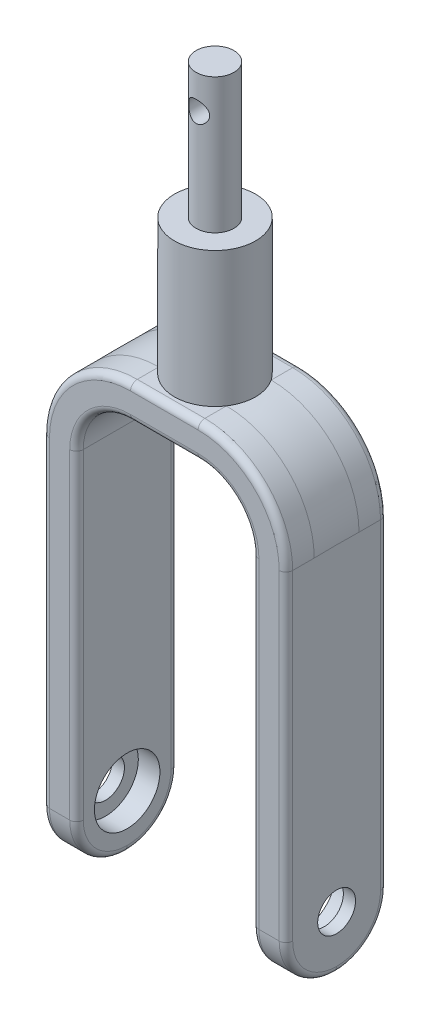
SolidWorks part; units mm, degrees
ref_plane "前视基准面" through (0, 0, 0) normal (0, 0, 1) x (1, 0, 0)
ref_plane "上视基准面" through (0, 0, 0) normal (0, 1, 0) x (1, 0, 0)
ref_plane "右视基准面" through (0, 0, 0) normal (1, 0, 0) x (0, 0, -1)
sketch "草图1" plane through (0, 0, 0) normal (0, 1, 0) x (1, 0, 0)
  line L1 (18, 7.5) -> (-18, 7.5)
  line L2 (18, 7.5) -> (18, -7.5)
  line L3 (18, -7.5) -> (-18, -7.5)
  line L4 (-18, 7.5) -> (-18, -7.5)
  line L5 (18, 7.5) -> (-18, -7.5) construction
  line L6 (18, -7.5) -> (-18, 7.5) construction
  point P0 (0, 0)
  point P6 (0, 0)
  point P7 (0, 0)
  point P8 (0, 0)
  point P9 (0, 0)
extrude "凸台-拉伸1" add sketch "草图1" against normal blind 68
sketch "草图2" plane through (0, 0, 0) normal (0, 1, 0) x (1, 0, 0)
  circle A0 centre (0, 0) radius 6
extrude "凸台-拉伸2" add sketch "草图2" along normal blind 20
sketch "草图7" plane through (0, 20, 0) normal (0, 1, 0) x (1, 0, 0)
  circle A0 centre (0, 0) radius 2.8
extrude "凸台-拉伸3" add sketch "草图7" along normal blind 20
sketch "草图8" plane through (0, 0, 0) normal (0, 0, 1) x (1, 0, 0)
  line L0 (0, 20) -> (0, 35) construction
  line L1 (6, 20) -> (-6, 20) construction
  circle A1 centre (0, 35) radius 1.55
  point P7 (0, 0)
extrude "切除-拉伸5" cut sketch "草图8" against normal through all both and the other way through all
sketch "草图3" plane through (0, 0, 7.5) normal (0, 0, 1) x (1, 0, 0)
  line L0 (-18, -68) -> (18, -68) construction
  line L1 (-13, -68) -> (13, -68)
  line L2 (-13, -68) -> (-13, -5)
  line L3 (-13, -5) -> (13, -5)
  line L4 (13, -68) -> (13, -5)
  point P6 (0, 0)
  point P7 (0, 0)
extrude "切除-拉伸1" cut sketch "草图3" against normal through all
fillet "圆角1" radius 8 2 edges at (13, -5, 0) (-13, -5, 0)
fillet "圆角5" radius 13 2 edges at (18, 0, 0) (-18, 0, 0)
fillet "圆角3" radius 7.5 4 edges at (15.5, -68, -7.5) (15.5, -68, 7.5) (-15.5, -68, -7.5) (-15.5, -68, 7.5)
fillet "圆角2" radius 1 28 edges at (-18, -36.75, -7.5) (0, 0, -7.5) (18, -36.75, -7.5) (18, -36.75, 7.5) (0, 0, 7.5) (-18, -36.75, 7.5) (-10.6569, -7.3431, 7.5) (0, -5, 7.5) (10.6569, -7.3431, 7.5) (13, -36.75, 7.5) (13, -36.75, -7.5) (10.6569, -7.3431, -7.5) (0, -5, -7.5) (-10.6569, -7.3431, -7.5) (-13, -36.75, -7.5) (-13, -36.75, 7.5) (13, -65.8033, 5.3033) (13, -65.8033, -5.3033) (-13, -65.8033, -5.3033) (-13, -65.8033, 5.3033) (-18, -65.8033, 5.3033) (-18, -65.8033, -5.3033) (18, -65.8033, -5.3033) (18, -65.8033, 5.3033) (-14.1924, -3.8076, -7.5) (14.1924, -3.8076, -7.5) (14.1924, -3.8076, 7.5) (-14.1924, -3.8076, 7.5)
sketch "草图4" plane through (18, 0, 0) normal (1, 0, 0) x (0, 0, -1)
  circle A0 centre (0, -60) radius 2.8
extrude "切除-拉伸2" cut sketch "草图4" against normal through all
sketch "草图6" plane through (13, 0, 0) normal (1, 0, 0) x (0, 0, -1)
  circle A0 centre (0, -60) radius 4.85
extrude "切除-拉伸4" cut sketch "草图6" along normal blind 3.2
mirror "镜向1" about plane through (0, 0, 0) normal (1, 0, 0) of "切除-拉伸4"
